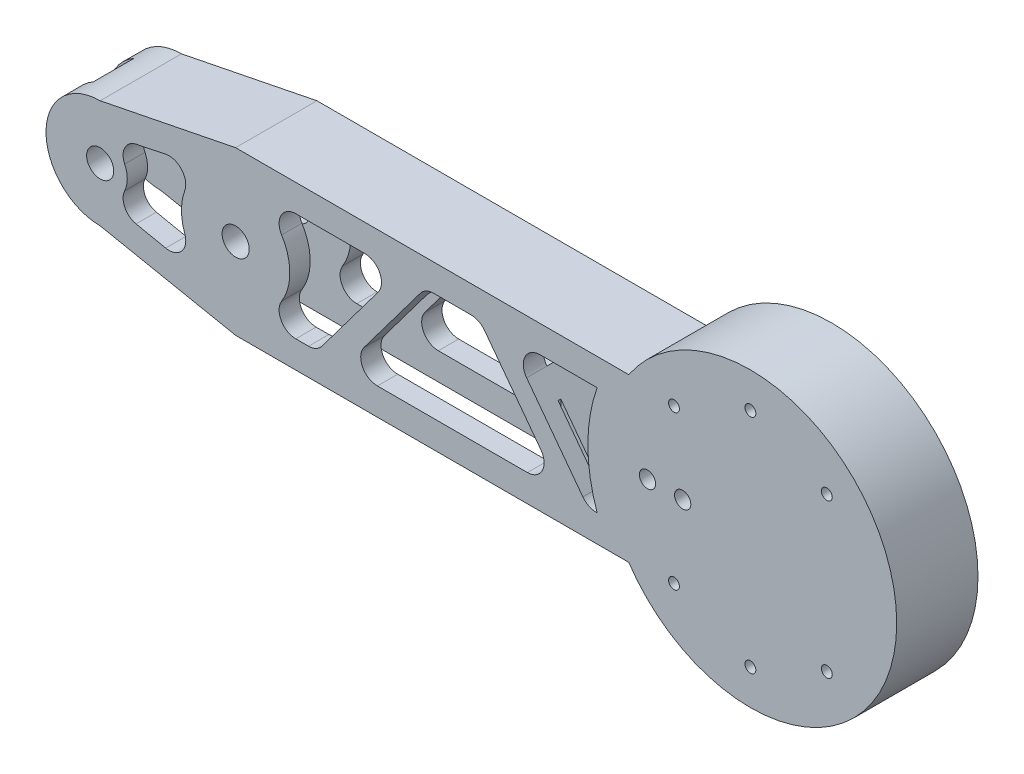
SolidWorks part; units mm, degrees
ref_plane "前视基准面" through (0, 0, 0) normal (0, 0, 1) x (1, 0, 0)
ref_plane "上视基准面" through (0, 0, 0) normal (0, 1, 0) x (1, 0, 0)
ref_plane "右视基准面" through (0, 0, 0) normal (1, 0, 0) x (0, 0, -1)
sketch "草图1" plane through (0, 0, 0) normal (1, 0, 0) x (0, 0, -1)
  line L0 (7.5, 0) -> (7.5, 15)
  line L11 (7.5, 15) -> (-7.5, 15)
  line L12 (-7.5, 15) -> (-7.5, -15)
  line L13 (-7.5, -15) -> (7.5, -15)
  line L14 (7.5, -15) -> (7.5, 0)
  dimension "D1" = 15
  dimension "D2" = 15
  dimension "D3" = 30
  dimension "D4" = 15
extrude "凸台-拉伸1" add sketch "草图1" along normal blind 60 and the other way blind 70
sketch "草图2" plane through (0, 0, 0) normal (0, 0, 1) x (1, 0, 0)
  line L2 (60, 15) -> (60, -15) construction
  circle A4 centre (60, 0) radius 27
  circle A5 centre (60, 0) radius 23.5
  dimension "D2" = 47
  dimension "D1" = 54
extrude "凸台-拉伸2" add sketch "草图2" along normal blind 7.5 and the other way blind 7.5
sketch "草图3" plane through (0, 0, 0) normal (0, 0, 1) x (1, 0, 0)
  line L0 (60, 15) -> (60, -15) construction
  circle A0 centre (60, 0) radius 24.5
  dimension "D1" = 49
extrude "切除-拉伸1" cut sketch "草图3" against normal blind 7.5 and the other way blind 7.5
sketch "草图4" plane through (0, 0, 7.5) normal (0, 0, 1) x (1, 0, 0)
  circle A1 centre (60, 0) radius 24.5
  dimension "D1" = 49
extrude "凸台-拉伸3" add sketch "草图4" against normal blind 3
sketch "草图5" plane through (0, 0, 4.5) normal (0, 0, -1) x (-1, 0, 0)
  line L0 (-36.5, 0) -> (-57.3178, 0) construction
  line L1 (-36.5, 0) -> (-36.5, 4)
  line L2 (-36.5, 4) -> (-40.5, 4)
  line L3 (-40.5, 4) -> (-45.5, 4)
  line L5 (-50.5, 0) -> (-50.5, 4)
  line L6 (-50.5, 4) -> (-45.5, 4)
  line L7 (-50.5, 0) -> (-50.5, -4)
  line L8 (-50.5, -4) -> (-36.5, -4)
  line L9 (-36.5, -4) -> (-36.5, 0)
  dimension "D1" = 4
  dimension "D2" = 4
  dimension "D3" = 5
  dimension "D4" = 14
  dimension "D5" = 4
extrude "凸台-拉伸4" add sketch "草图5" along normal blind 2.58
sketch "草图6" plane through (0, 0, 4.5) normal (0, 0, -1) x (-1, 0, 0)
  line L0 (-60, 29.757) -> (-60, -28.858) construction
  line L1 (-93.4216, 0) -> (-30.7153, 0) construction
  circle A0 centre (-60, 0) radius 20.5 construction
  circle A1 centre (-60, 20.5) radius 1
  circle A5 centre (-60, -20.5) radius 1
  circle A9 centre (-80.5, 0) radius 1 [skipped]
  circle A10 centre (-39.5, 0) radius 1 [skipped]
  circle A11 centre (-45.5043, 14.4957) radius 1 [skipped]
  circle A12 centre (-74.4957, 14.4957) radius 1 [skipped]
  circle A13 centre (-74.4957, -14.4957) radius 1 [skipped]
  circle A14 centre (-45.5043, -14.4957) radius 1 [skipped]
  circle A15 centre (-60, 0) radius 20 construction
  circle A16 centre (-45.8949, 14.1791) radius 1
  circle A17 centre (-74.1051, 14.1791) radius 1
  circle A18 centre (-74.1051, -14.1791) radius 1
  circle A19 centre (-45.8949, -14.1791) radius 1
  point P28 (-60, 0)
  dimension "D1" = 41
  dimension "D2" = 2
  dimension "D4" = 40
  dimension "D6" = 2
  dimension "D3" = 8
extrude "切除-拉伸2" cut sketch "草图6" against normal blind 3
sketch "草图7" plane through (0, 0, 1.92) normal (0, 0, -1) x (-1, 0, 0)
  circle A0 centre (-47.5, 0) radius 1.5
  circle A1 centre (-41, 0) radius 1.5
  dimension "D2" = 3
  dimension "D4" = 3
extrude "切除-拉伸3" cut sketch "草图7" against normal blind 5.58
sketch "草图8" plane through (-70, 0, 0) normal (-1, 0, 0) x (0, 0, 1)
  line L1 (-7.5, 15) -> (7.5, 15) construction
  line L2 (0, 15) -> (-3.75, 15)
  line L3 (-7.5, 15) -> (7.5, 15) construction
  line L4 (-3.75, 15) -> (-3.75, -15)
  line L5 (7.5, -15) -> (-7.5, -15) construction
  line L6 (-3.75, -15) -> (3.75, -15)
  line L7 (7.5, -15) -> (-7.5, -15) construction
  line L8 (3.75, -15) -> (3.75, 15)
  line L9 (3.75, 15) -> (0, 15)
  dimension "D1" = 3.75
  dimension "D2" = 7.5
extrude "切除-拉伸4" cut sketch "草图8" against normal blind 97
ref_plane "基准面1" through (36.5, 0, 0) normal (1, 0, 0) x (0, 0, -1)
sketch "草图9" plane through (36.5, 0, 0) normal (1, 0, 0) x (0, 0, -1)
  line L9 (3.75, 0) -> (3.75, 9.1)
  line L10 (3.75, 0) -> (3.75, 9.1)
  line L11 (3.75, 9.1) -> (-4.5, 9.1)
  line L12 (-4.5, 9.1) -> (-4.5, -9.1)
  line L13 (3.75, 0) -> (3.75, -9.1)
  line L14 (3.75, -9.1) -> (-4.5, -9.1)
  dimension "D1" = 9.1
  dimension "D2" = 8.25
  dimension "D3" = 18.2
  dimension "D4" = 9.1
extrude "切除-拉伸5" cut sketch "草图9" against normal blind 15 and the other way blind 1 contours L14 L13 L9 L11 L12 region at (36.5, 0, 0.375)
sketch "草图10" plane through (0, 0, 0) normal (0, 0, 1) x (1, 0, 0)
  line L0 (0, 0) -> (-60, 0) construction
  line L1 (-60, 0) -> (-35, 0) construction
  line L2 (-35, 15) -> (-60, 10)
  line L3 (-70, 15) -> (37.5501, 15) construction
  line L4 (-60, 0) -> (-70, 0) construction
  line L5 (-35, -15) -> (-60, -10)
  line L6 (-53.3819, 6.3701) -> (-47.9103, 7.5028)
  line L7 (-53.3819, -6.3701) -> (-47.9103, -7.5028)
  line L8 (-35, 10) -> (35, 10) construction
  line L9 (-35, -10) -> (35, -10) construction
  line L10 (-23.901, 10) -> (-11.1594, 10)
  line L12 (-23.901, -10) -> (-21.5399, -10)
  line L13 (-19.0761, -8.7681) -> (-8.6957, 5.0725)
  line L14 (-5, 10) -> (0, 10) construction
  line L15 (-20, -10) -> (-15, -10) construction
  line L16 (-11.3043, -5.0725) -> (-0.9239, 8.7681)
  line L17 (1.5399, 10) -> (8.4601, 10)
  line L18 (5, 12.2067) -> (5, -12.3113)
  line L19 (-8.8406, -10) -> (5, -10)
  line L20 (5, -10) -> (18.8406, -10)
  line L21 (21.3043, -5.0725) -> (10.9239, 8.7681)
  line L22 (10, 10) -> (15, 10) construction
  line L23 (18.6957, 5.0725) -> (29.0761, -8.7681)
  line L24 (31.5399, -10) -> (31.7157, -10)
  line L25 (21.1594, 10) -> (31.7157, 10)
  line L27 (-35, 15) -> (-70, 15)
  line L28 (-70, 15) -> (-70, -15) construction
  line L29 (-70, 15) -> (-70, -15)
  line L30 (-70, -15) -> (-35, -15)
  circle A0 centre (-60, 0) radius 2.5
  circle A1 centre (-35, 0) radius 2.5
  arc A6 (-60, -10) -> (-60, 10) centre (-60, 0) cw
  arc A7 (-55.4836, 2.1452) -> (-55.4836, -2.1452) centre (-60, 0) cw
  arc A8 (-44.3932, 3.4305) -> (-44.3932, -3.4305) centre (-35, 0) ccw
  arc A10 (-26.5143, 5.2909) -> (-26.5143, -5.2909) centre (-35, 0) cw
  arc A11 (-55.4836, 2.1452) -> (-53.3819, 6.3701) centre (-52.7737, 3.4323) cw
  arc A12 (-53.3819, -6.3701) -> (-55.4836, -2.1452) centre (-52.7737, -3.4323) cw
  arc A13 (-44.3932, 3.4305) -> (-47.9103, 7.5028) centre (-47.286, 4.487) ccw
  arc A14 (-47.9103, -7.5028) -> (-44.3932, -3.4305) centre (-47.286, -4.487) ccw
  arc A15 (-26.5143, 5.2909) -> (-23.901, 10) centre (-23.901, 6.9203) cw
  arc A16 (-23.901, -10) -> (-26.5143, -5.2909) centre (-23.901, -6.9203) cw
  arc A17 (-11.1594, 10) -> (-8.6957, 5.0725) centre (-11.1594, 6.9203) cw
  arc A18 (-21.5399, -10) -> (-19.0761, -8.7681) centre (-21.5399, -6.9203) ccw
  arc A19 (-8.8406, -10) -> (-11.3043, -5.0725) centre (-8.8406, -6.9203) cw
  arc A20 (1.5399, 10) -> (-0.9239, 8.7681) centre (1.5399, 6.9203) ccw
  arc A21 (10.9239, 8.7681) -> (8.4601, 10) centre (8.4601, 6.9203) ccw
  arc A22 (18.8406, -10) -> (21.3043, -5.0725) centre (18.8406, -6.9203) ccw
  arc A23 (18.6957, 5.0725) -> (21.1594, 10) centre (21.1594, 6.9203) cw
  arc A24 (31.5399, -10) -> (29.0761, -8.7681) centre (31.5399, -6.9203) cw
  arc A26 (31.7157, 10) -> (31.7157, -10) centre (60, 0) ccw
  point P45 (-60, 5)
  point P48 (-60, -5)
  point P51 (-37.8485, 9.5857)
  point P54 (-37.8485, -9.5857)
  point P77 (25, -10)
  point P83 (30, -10)
  dimension "D2" = 5
  dimension "D4" = 5
  dimension "D5" = 3
  dimension "D6" = 3
  dimension "D15" = 3.0797
  dimension "D16" = 3.0797
  dimension "D17" = 3.0797
  dimension "D8" = 3.0797
  dimension "D9" = 3.0797
  dimension "D18" = 3.0797
  dimension "D19" = 3.0797
  dimension "D20" = 3.0797
  dimension "D21" = 3.0797
  dimension "D22" = 3.0797
  dimension "D23" = 3.0797
  dimension "D24" = 3.0797
  dimension "D1" = 60
  dimension "D3" = 25
  dimension "D10" = 5
  dimension "D11" = 5
  dimension "D12" = 10
  dimension "D13" = 20
  dimension "D14" = 5
extrude "切除-拉伸6" cut sketch "草图10" against normal blind 7.5 and the other way through all contours L29 A6 L2 L27 | L5 A6 L29 L30 | A0 | L7 A14 A8 A13 L6 A11 A7 A12 | A1 | L12 A18 L13 A17 L10 A15 A10 A16 | L17 A20 L16 A19 L19 L18 | L20 A22 L21 A21 L17 L18 | A26 L25 A23 L23 A24 L24 region at (-59.2224, -12.1305, 0) region at (-59.2224, 12.1305, 0) region at (-49.8088, 0, 0) region at (-18.9131, 1.6478, 0) region at (-1.6337, -1.7794, 0) region at (11.6337, -1.7794, 0) region at (25.8146, 2.8144, 0) region at (-60, 0, 0) region at (-35, 0, 0)
sketch "草图11" plane through (0, 0, 0) normal (0, 0, 1) x (1, 0, 0)
  line L6 (-77.8246, 0) -> (90.0052, 0) construction
  line L8 (-65, 8.6603) -> (-63.75, 6.4952)
  line L9 (-35, 15) -> (-60, 10)
  line L10 (34.0192, 15) -> (-35, 15)
  line L11 (-34.5192, 12.5962) -> (32.7725, 12.5962)
  line L12 (-60, 7.5) -> (-34.5192, 12.5962)
  arc A7 (-63.75, 6.4952) -> (-60, 7.5) centre (-60, 0) cw
  arc A8 (-60, 10) -> (-65, 8.6603) centre (-60, 0) ccw
  arc A9 (32.7725, 12.5962) -> (34.0192, 15) centre (60, 0) cw
sketch "草图12" plane through (0, 0, 0) normal (0, 0, 1) x (1, 0, 0)
  line L1 (21.3043, -5.0725) -> (10.9239, 8.7681) construction
  line L2 (13.6957, 5.0725) -> (21.3043, -5.0725)
  line L4 (18.6957, 5.0725) -> (29.0761, -8.7681) construction
  line L5 (26.3043, -5.0725) -> (18.6957, 5.0725)
  line L27 (18.6957, 5.0725) -> (21.3043, 5.0725) construction
  line L28 (20, 6.0507) -> (20, -8.2976) construction
  line L29 (29.9814, -9.9752) -> (24.9814, -9.9752)
  line L30 (21.3043, -5.0725) -> (24.9814, -9.9752)
  line L31 (26.3043, -5.0725) -> (29.9814, -9.9752)
  line L32 (26.3043, -5.0725) -> (18.6957, 5.0725)
  line L33 (13.6957, 5.0725) -> (21.3043, -5.0725)
  line L34 (18.6957, 5.0725) -> (13.6957, 5.0725)
  line L36 (-10, 8.4713) -> (-10, 3.7821) construction
  line L37 (-8.6957, 5.0725) -> (-13.8859, -1.8478)
  line L38 (-13.8859, -1.8478) -> (-3.3621, 5.5173)
  line L39 (-3.3621, 5.5173) -> (-0.9239, 8.7681)
  line L40 (-0.9239, 8.7681) -> (-8.6957, 8.7681)
  arc A4 (-8.6957, 5.0725) -> (-8.6957, 8.7681) centre (-11.1594, 6.9203) ccw
extrude "凸台-拉伸6" add sketch "草图12" along normal blind 4 and the other way blind 4 contours L5 L34 L2 L30 L29 L31 | A4 L37 L38 L39 L40 region at (21.8385, -2.4514, 0) region at (-6.7827, 5.2396, 0)
extrude "凸台-拉伸7" add sketch "草图11" along normal blind 4 and the other way blind 4
